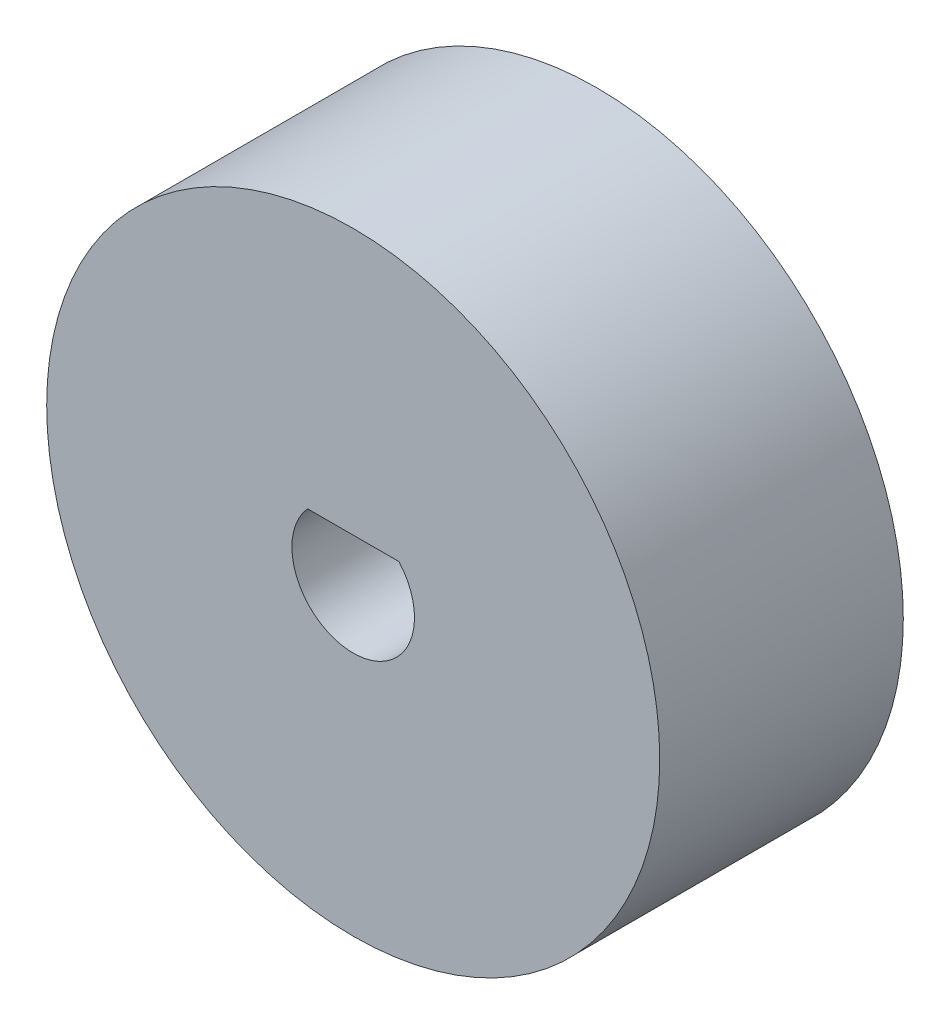
SolidWorks part; units mm, degrees
ref_plane "Front Plane" through (0, 0, 0) normal (0, 0, 1) x (1, 0, 0)
ref_plane "Top Plane" through (0, 0, 0) normal (0, 1, 0) x (1, 0, 0)
ref_plane "Right Plane" through (0, 0, 0) normal (1, 0, 0) x (0, 0, -1)
sketch "Sketch1" plane through (0, 0, 0) normal (0, 0, 1) x (1, 0, 0)
  line L0 (0, 0) -> (12707.853, 0) construction
  line L1 (0, 0) -> (0, -12707.853) construction
  line L2 (-1.118, 1) -> (1.118, 1)
  circle A0 centre (0, 0) radius 7.5
  arc A1 (-1.118, 1) -> (1.118, 1) centre (0, 0) ccw
  circle A2 centre (0, 0) radius 2.5
  dimension "D1" = 15
  dimension "D2" = 3
  dimension "D4" = 5
  dimension "D3" = 1
extrude "Boss-Extrude2" add sketch "Sketch1" along normal mid plane 5.96 contours A0 A2 region at (-7.2879, 0, 0)
extrude "Boss-Extrude3" add sketch "Sketch1<5>" along normal up to surface and the other way up to surface contours A2 A1 L2 region at (-2.4293, 0, 0) up to face at (2.5, 0, 2.98) other way up to face at (2.5, 0, -2.98)
sketch "Sketch1<5>" plane through (0, 0, 0) normal (0, 0, 1) x (1, 0, 0) same geometry as "Sketch1"
